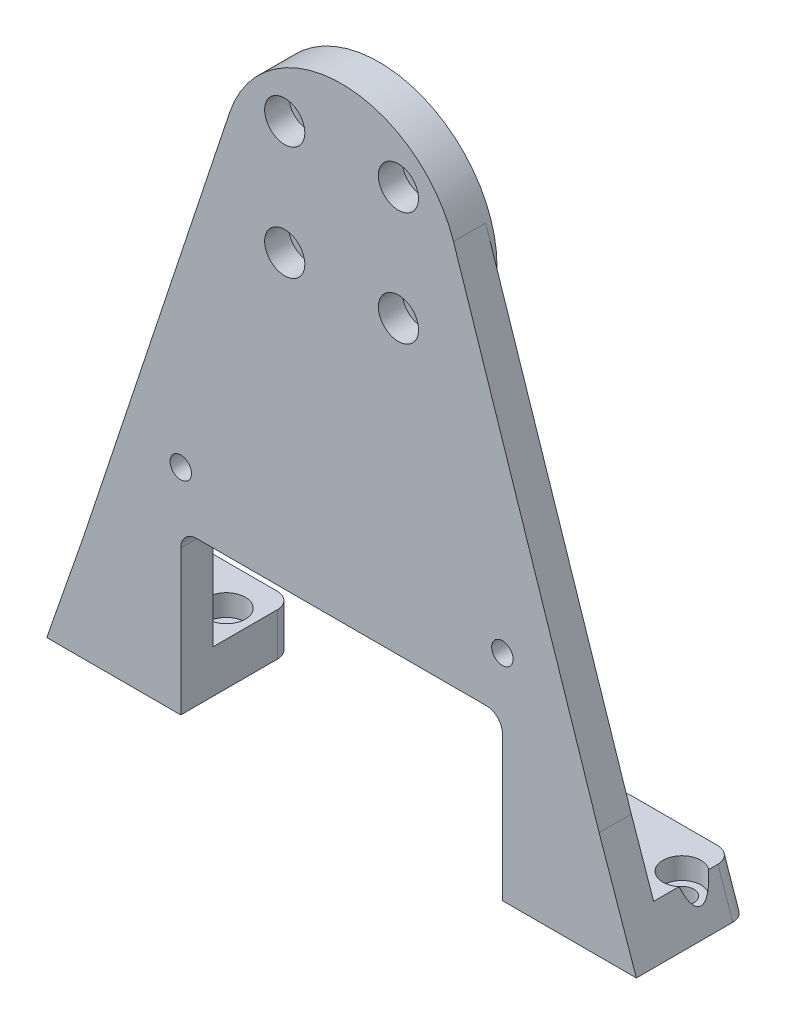
SolidWorks part; units mm, degrees
ref_plane "Front Plane" through (0, 0, 0) normal (0, 0, 1) x (1, 0, 0)
ref_plane "Top Plane" through (0, 0, 0) normal (0, 1, 0) x (1, 0, 0)
ref_plane "Right Plane" through (0, 0, 0) normal (1, 0, 0) x (0, 0, -1)
sketch "Sketch1" plane through (0, 0, 0) normal (0, 0, 1) x (1, 0, 0)
  line L0 (0, 0) -> (0, 33.5533) construction
  line L1 (0, 0) -> (10.6066, 10.6066) construction
  circle A0 centre (0, 0) radius 22
  circle A1 centre (10.6066, 10.6066) radius 2.2
  circle A2 centre (10.6066, -10.6066) radius 2.2
  circle A3 centre (-10.6066, -10.6066) radius 2.2
  circle A4 centre (-10.6066, 10.6066) radius 2.2
  point P14 (0, 0)
  dimension "D1" = 44
  dimension "D3" = 4.4
  dimension "D2" = 15
  dimension "D5" = 45
  dimension "D4" = 4
extrude "Boss-Extrude1" add sketch "Sketch1" along normal blind 1
sketch "Sketch2" plane through (0, 0, 1) normal (0, 0, 1) x (1, 0, 0)
  line L0 (-55, -95) -> (55, -95)
  line L1 (55, -95) -> (48.055, -75)
  line L3 (-48.055, -75) -> (-55, -95)
  line L4 (-48.055, -75) -> (-20.8813, 6.926)
  line L5 (48.055, -75) -> (20.8813, 6.926)
  line L7 (-30, -95) -> (30, -95)
  line L8 (-30, -95) -> (-30, -65)
  line L9 (-30, -65) -> (30, -65)
  line L10 (30, -95) -> (30, -65)
  circle A0 centre (0, 0) radius 22 construction
  circle A1 centre (10.6066, 10.6066) radius 2.2
  circle A2 centre (10.6066, 10.6066) radius 2.2
  circle A3 centre (10.6066, -10.6066) radius 2.2
  circle A4 centre (10.6066, -10.6066) radius 2.2
  circle A5 centre (-10.6066, -10.6066) radius 2.2
  circle A6 centre (-10.6066, -10.6066) radius 2.2
  circle A7 centre (-10.6066, 10.6066) radius 2.2
  circle A8 centre (-10.6066, 10.6066) radius 2.2
  arc A9 (20.8813, 6.926) -> (-20.8813, 6.926) centre (0, 0) ccw
  circle A10 centre (-30, -55) radius 2
  circle A11 centre (30, -55) radius 2
  point P14 (0, -95)
  point P27 (0, -65)
  circle M16 centre (-10.6066, -10.6066) radius 2.2
  circle M17 centre (10.6066, 10.6066) radius 2.2
  circle M18 centre (0, 0) radius 22
  circle M19 centre (10.6066, -10.6066) radius 2.2
  circle M20 centre (-10.6066, 10.6066) radius 2.2
  dimension "D15" = 4
  dimension "D5" = 96.11
  dimension "D6" = 110
  dimension "D7" = 95
  dimension "D8" = 6.945
  dimension "D9" = 20
  dimension "D10" = 30
  dimension "D11" = 60
  dimension "D12" = 60
  dimension "D13" = 30
  dimension "D14" = 10
  dimension "D1" = 0
  dimension "D2" = 0
  dimension "D3" = 0
  dimension "D4" = 0
extrude "Boss-Extrude2" add sketch "Sketch2" along normal blind 6 contours L10 L0 L1 L5 L4 L3 L8 L9 M18 | M18 M17 M19 M20 M16 region at (0, -51.1702, 1) region at (0, 0, 1)
sketch "Sketch3" plane through (0, -95, 0) normal (0, -1, 0) x (-1, 0, 0)
  line L0 (-30, -7) -> (-30, -1) construction
  line L1 (-55, -1) -> (-30, -1)
  line L2 (-55, -1) -> (-55, 14)
  line L3 (-55, 14) -> (-30, 14)
  line L4 (-30, -1) -> (-30, 14)
  line L5 (0, 0) -> (0, 14.6522) construction
  line L6 (30, -1) -> (30, 14)
  line L7 (55, 14) -> (30, 14)
  line L8 (55, -1) -> (55, 14)
  line L9 (55, -1) -> (30, -1)
  circle A0 centre (-35, 6.5) radius 2.2
  circle A1 centre (-50, 6.5) radius 2.2
  circle A2 centre (50, 6.5) radius 2.2
  circle A3 centre (35, 6.5) radius 2.2
  point P11 (-30, 6.5)
  dimension "D4" = 4.4
  dimension "D1" = 15
  dimension "D2" = 15
  dimension "D3" = 5
extrude "Boss-Extrude3" add sketch "Sketch3" against normal blind 8
sketch "Sketch4" plane through (0, 0, 1) normal (0, 0, 1) x (1, 0, 0)
  line L0 (-55, -95) -> (-52.222, -87)
  line L1 (-52.222, -87) -> (-55, -87)
  line L2 (-55, -87) -> (-55, -95)
  line L3 (55, -95) -> (55, -87)
  line L4 (55, -87) -> (52.222, -87)
  line L5 (52.222, -87) -> (55, -95)
extrude "Cut-Extrude1" cut sketch "Sketch4" against normal through all
sketch "Sketch5" plane through (0, -87, 0) normal (0, 1, 0) x (1, 0, 0)
  circle A0 centre (-50, 6.5) radius 3.55
  circle A1 centre (-35, 6.5) radius 3.55
  circle A2 centre (35, 6.5) radius 3.55
  circle A3 centre (50, 6.5) radius 3.55
  dimension "D1" = 7.1
extrude "Cut-Extrude2" cut sketch "Sketch5" against normal blind 4
fillet "Fillet1" radius 3 6 edges at (-53.611, -91, -14) (-30, -91, -14) (53.611, -91, -14) (30, -91, -14) (-30, -65, 4) (30, -65, 4)
sketch "Sketch6" plane through (0, 0, 7) normal (0, 0, 1) x (1, 0, 0)
  circle A0 centre (-10.6066, 10.6066) radius 3.75
  circle A1 centre (10.6066, 10.6066) radius 3.75
  circle A2 centre (10.6066, -10.6066) radius 3.75
  circle A3 centre (-10.6066, -10.6066) radius 3.75
  dimension "D1" = 7.5
extrude "Cut-Extrude3" cut sketch "Sketch6" against normal blind 4.5
